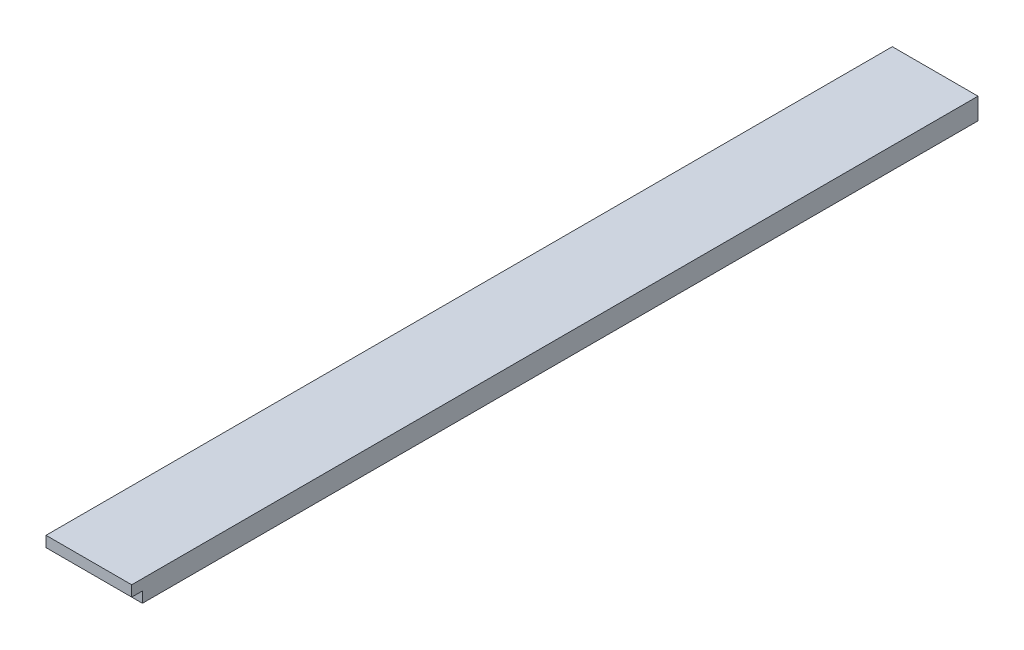
SolidWorks part; units mm, degrees
ref_plane "Front Plane" through (0, 0, 0) normal (0, 0, 1) x (1, 0, 0)
ref_plane "Top Plane" through (0, 0, 0) normal (0, 1, 0) x (1, 0, 0)
ref_plane "Right Plane" through (0, 0, 0) normal (1, 0, 0) x (0, 0, -1)
sketch "Sketch1" plane through (0, 0, 0) normal (0, 0, 1) x (1, 0, 0)
  line L0 (0, 12.7) -> (0, 6.35)
  line L1 (0, 6.35) -> (12.7, 6.35)
  line L2 (12.7, 6.35) -> (12.7, 0)
  line L3 (12.7, 0) -> (50.8, 0)
  line L4 (50.8, 0) -> (50.8, 12.7)
  line L5 (50.8, 12.7) -> (0, 12.7)
  dimension "D1" = 6.35
  dimension "D2" = 6.35
  dimension "D3" = 12.7
  dimension "D4" = 50.8
extrude "Boss-Extrude1" add sketch "Sketch1" along normal blind 501.65
sketch "Sketch2" plane through (0, 0, 0) normal (0, -1, 0) x (1, 0, 0)
  line L0 (50.8, 501.65) -> (50.8, 0) construction
  line L1 (50.8, 495.3) -> (12.7, 495.3)
  line L2 (50.8, 495.3) -> (50.8, 501.65)
  line L3 (50.8, 501.65) -> (12.7, 501.65)
  line L4 (12.7, 495.3) -> (12.7, 501.65)
  dimension "D1" = 6.35
extrude "Cut-Extrude1" cut sketch "Sketch2" against normal blind 6.35
